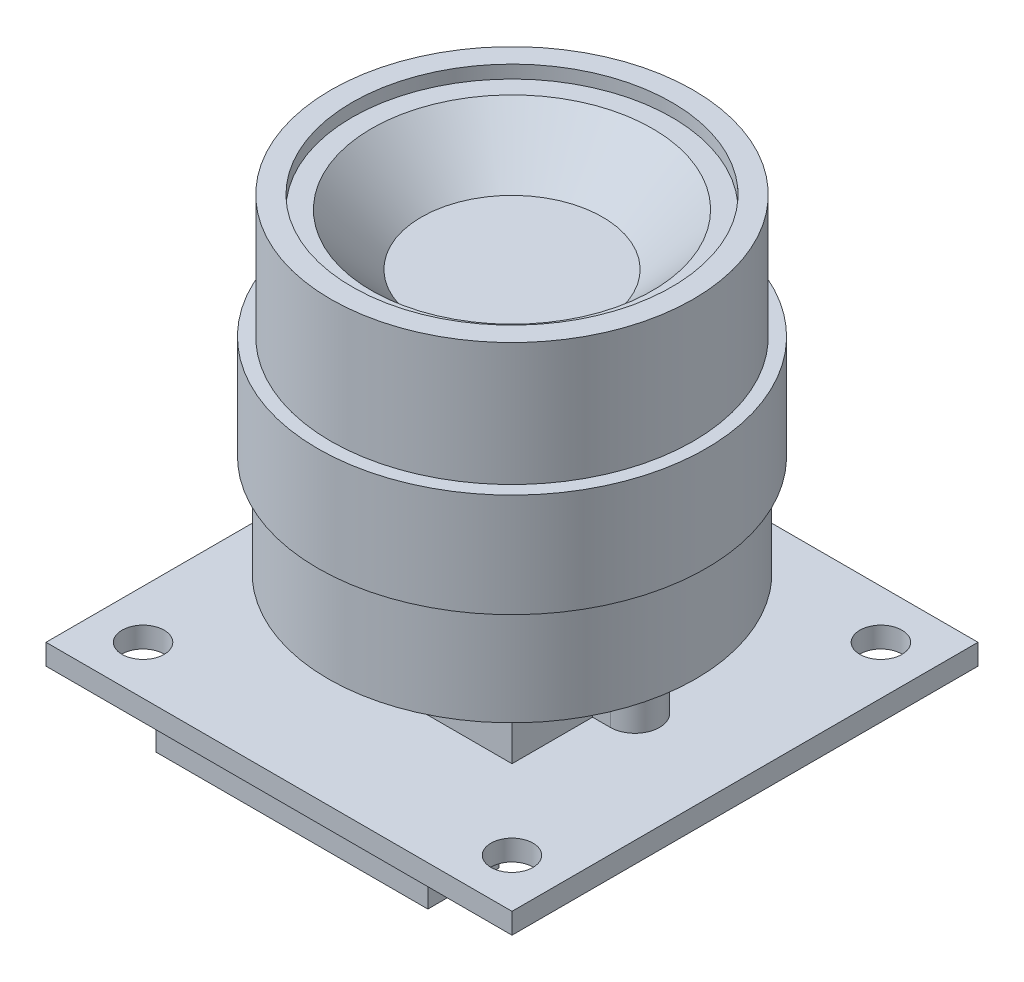
SolidWorks part; units mm, degrees
ref_plane "Front Plane" through (0, 0, 0) normal (0, 0, 1) x (1, 0, 0)
ref_plane "Top Plane" through (0, 0, 0) normal (0, 1, 0) x (1, 0, 0)
ref_plane "Right Plane" through (0, 0, 0) normal (1, 0, 0) x (0, 0, -1)
sketch "Sketch1" plane through (0, 0, 0) normal (0, 1, 0) x (1, 0, 0)
  line L1 (-18, -18) -> (18, -18)
  line L2 (-18, -18) -> (-18, 18)
  line L3 (-18, 18) -> (18, 18)
  line L4 (18, -18) -> (18, 18)
  line L5 (-18, -18) -> (18, 18) construction
  line L6 (-18, 18) -> (18, -18) construction
  point P0 (0, 0)
  dimension "D1" = 36
extrude "Boss-Extrude1" add sketch "Sketch1" along normal blind 1.6
hole_wizard "Ø3.2 (3.2) Diameter Hole1" positions "Sketch3" profile "Sketch2" hole size "Ø3.2" standard "ANSI Metric" end condition through all
sketch "Sketch3" plane through (0, 1.6, 0) normal (0, 1, 0) x (1, 0, 0)
  line L0 (-14.25, 14.25) -> (14.25, 14.25) construction
  line L1 (14.25, 14.25) -> (14.25, -14.25) construction
  line L2 (14.25, -14.25) -> (-14.25, -14.25) construction
  line L3 (-14.25, -14.25) -> (-14.25, 14.25) construction
  line L5 (-14.25, 0) -> (-18, 0) construction
  line L6 (-18, 18) -> (-18, -18) construction
  line L10 (-18, -18) -> (18, -18) construction
  line L12 (0, -14.25) -> (0, -18) construction
  point P0 (-14.25, 14.25)
  point P2 (14.25, 14.25)
  point P4 (14.25, -14.25)
  point P6 (-14.25, -14.25)
  dimension "D1" = 28.5
  dimension "D2" = 28.5
sketch "Sketch2" plane through (-14.25, 1.6, -14.25) normal (1, 0, 0) x (0, 0, 1)
  line L0 (0, 0) -> (0, 1.6)
  line L1 (0, 1.6) -> (1.625, 1.6)
  line L2 (1.625, 1.6) -> (1.625, 0)
  line L5 (1.625, 0) -> (0, 0)
  line L11 (0, -6.35) -> (0, 107.95) construction
  dimension "Thru Hole Dia." = 3.25
  dimension "Thru Hole Depth" = 1.6
sketch "Sketch4" plane through (0, 1.6, 0) normal (0, 1, 0) x (1, 0, 0)
  line L0 (-9.5, 0) -> (9.5, 0) construction
  line L1 (-8.125, -8.125) -> (8.125, -8.125)
  line L2 (-8.125, -8.125) -> (-8.125, -1.9)
  line L3 (-8.125, 8.125) -> (8.125, 8.125)
  line L4 (8.125, -8.125) -> (8.125, -1.9)
  line L5 (-8.125, -8.125) -> (8.125, 8.125) construction
  line L6 (-8.125, 8.125) -> (8.125, -8.125) construction
  line L7 (-9.5, 1.9) -> (-8.125, 1.9)
  line L8 (-9.5, -1.9) -> (-8.125, -1.9)
  line L9 (-8.125, 1.9) -> (-8.125, 8.125)
  line L10 (8.125, 1.9) -> (9.5, 1.9)
  line L11 (8.125, 1.9) -> (8.125, 8.125)
  line L12 (8.125, -1.9) -> (9.5, -1.9)
  arc A0 (9.5, 1.9) -> (9.5, -1.9) centre (9.5, 0) cw
  arc A1 (-9.5, 1.9) -> (-9.5, -1.9) centre (-9.5, 0) ccw
  point P0 (0, 0)
  dimension "D4" = 1.9
  dimension "D1" = 16.25
  dimension "D2" = 16.25
  dimension "D3" = 19
extrude "Boss-Extrude2" add sketch "Sketch4" along normal blind 4.65
sketch "Sketch5" plane through (0, 6.25, 0) normal (0, 1, 0) x (1, 0, 0)
  circle A0 centre (0, 0) radius 14.2
  dimension "D1" = 28.4
extrude "Boss-Extrude3" add sketch "Sketch5" along normal blind 7.8
sketch "Sketch6" plane through (0, 14.05, 0) normal (0, 1, 0) x (1, 0, 0)
  circle A0 centre (0, 0) radius 15
  dimension "D1" = 30
extrude "Boss-Extrude4" add sketch "Sketch6" along normal blind 8
sketch "Sketch7" plane through (0, 22.05, 0) normal (0, 1, 0) x (1, 0, 0)
  circle A0 centre (0, 0) radius 14
  dimension "D1" = 28
extrude "Boss-Extrude5" add sketch "Sketch7" along normal blind 9.5
sketch "Sketch8" plane through (0, 0, 0) normal (0, -1, 0) x (1, 0, 0)
  line L0 (-18, 18) -> (18, 18) construction
  line L3 (-10.5, 11.5) -> (10.5, 11.5)
  line L4 (-10.5, 11.5) -> (-10.5, 17)
  line L5 (-10.5, 17) -> (10.5, 17)
  line L6 (10.5, 11.5) -> (10.5, 17)
  line L7 (-10.5, 11.5) -> (10.5, 17) construction
  line L8 (-10.5, 17) -> (10.5, 11.5) construction
  point P2 (0, 14.25)
  dimension "D1" = 21
  dimension "D2" = 5.5
  dimension "D3" = 1
extrude "Boss-Extrude6" add sketch "Sketch8" along normal blind 2.5
sketch "Sketch9" plane through (0, 0, 0) normal (0, 0, 1) x (1, 0, 0)
  line L0 (0, 31.55) -> (0, 26.55)
  line L1 (14, 31.55) -> (-14, 31.55) construction
  line L2 (0, 31.55) -> (12.35, 31.55)
  line L3 (12.35, 31.55) -> (12.35, 30.55)
  line L4 (12.35, 30.55) -> (10.85, 30.55)
  line L5 (10.85, 30.55) -> (7, 26.55)
  line L6 (7, 26.55) -> (0, 26.55)
  dimension "D1" = 12.35
  dimension "D2" = 7
  dimension "D3" = 1
  dimension "D4" = 4
  dimension "D5" = 1.5
revolve "Cut-Revolve1" cut sketch "Sketch9" angle 360 about L0
sketch "Cable Reference" plane through (0, 0, 17) normal (0, 0, 1) x (1, 0, 0)
  line L0 (0, 0) -> (0, -2.5) construction
  line L1 (10.5, 0) -> (-10.5, 0) construction
  line L2 (10.5, -2.5) -> (-10.5, -2.5) construction
  line L3 (-8, -1.25) -> (8, -1.25) construction
  point P8 (0, -1.25)
  dimension "D1" = 16
